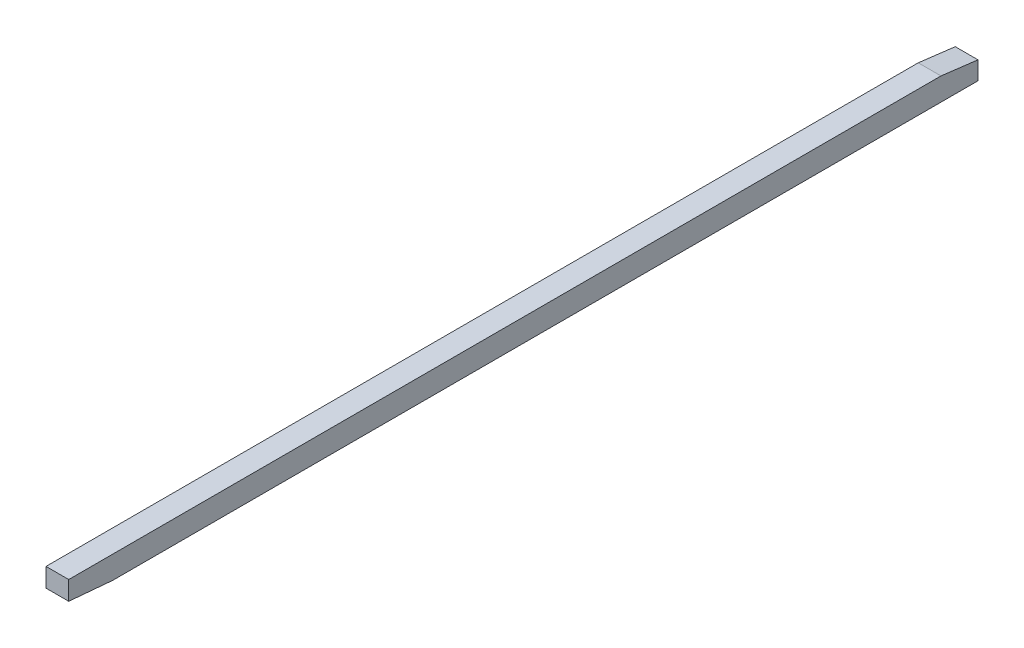
SolidWorks part; units mm, degrees
ref_plane "Front Plane" through (0, 0, 0) normal (0, 0, 1) x (1, 0, 0)
ref_plane "Top Plane" through (0, 0, 0) normal (0, 1, 0) x (1, 0, 0)
ref_plane "Right Plane" through (0, 0, 0) normal (1, 0, 0) x (0, 0, -1)
sketch "Sketch1" plane through (0, 0, 0) normal (0, 0, 1) x (1, 0, 0)
  line L1 (0, 0) -> (-2.54, 0)
  line L2 (0, 0) -> (0, 2.54)
  line L3 (0, 2.54) -> (-2.54, 2.54)
  line L4 (-2.54, 0) -> (-2.54, 2.54)
  dimension "D1" = 2.54
  dimension "D2" = 2.54
extrude "Boss-Extrude1" add sketch "Sketch1" along normal blind 101.6
chamfer "Chamfer1" distance 4.92 angle 5 1 edges at (-1.27, 0, 101.6) first distance on face at (-1.27, 0, 50.8)
chamfer "Chamfer2" distance 0.508 angle 83 1 edges at (-1.27, 2.54, 0) first distance on face at (-1.27, 1.27, 0)
